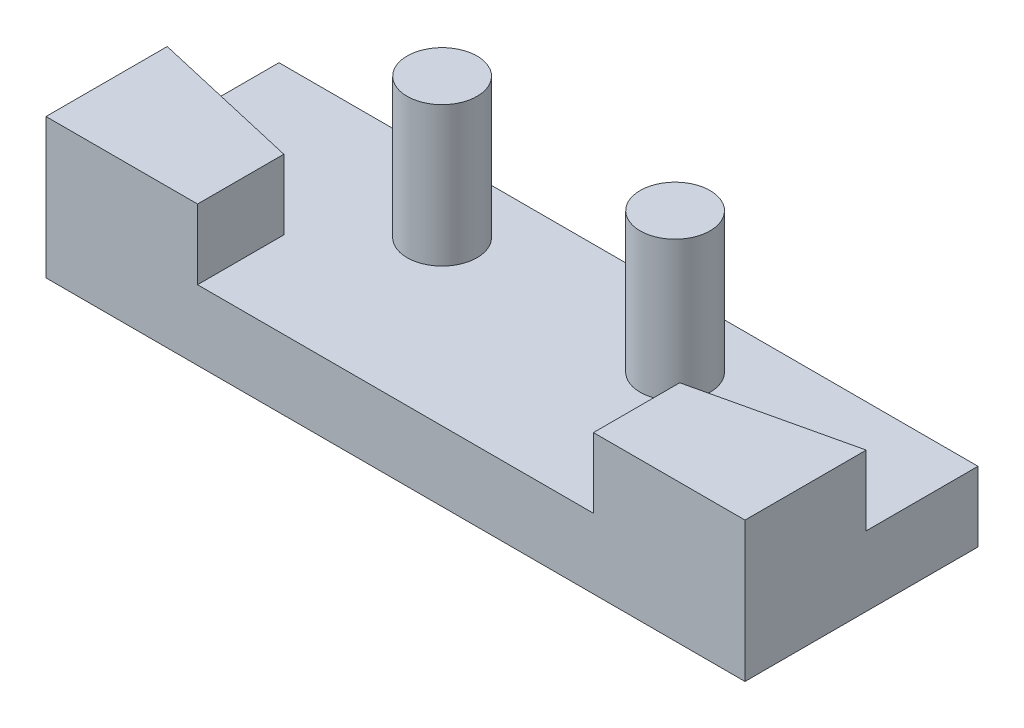
SolidWorks part; units mm, degrees
ref_plane "Front Plane" through (0, 0, 0) normal (0, 0, 1) x (1, 0, 0)
ref_plane "Top Plane" through (0, 0, 0) normal (0, 1, 0) x (1, 0, 0)
ref_plane "Right Plane" through (0, 0, 0) normal (1, 0, 0) x (0, 0, -1)
sketch "Sketch2" plane through (0, 0, 0) normal (0, 1, 0) x (1, 0, 0)
  line L1 (0, 0) -> (30, 0)
  line L2 (0, 0) -> (0, -10)
  line L3 (0, -10) -> (30, -10)
  line L4 (30, 0) -> (30, -10)
  dimension "D1" = 30
  dimension "D2" = 10
extrude "Boss-Extrude2" add sketch "Sketch2" along normal blind 6
sketch "Sketch4" plane through (0, 6, 0) normal (0, 1, 0) x (1, 0, 0)
  line L0 (30, 0) -> (0, 0) construction
  line L1 (0, 0) -> (0, -10) construction
  line L2 (10, -3) -> (4.3125, -1.6869) construction
  line L3 (10, -3) -> (9.1002, -6.8975) construction
  line L4 (9.1002, -6.8975) -> (0, -4.7965) construction
  line L5 (0, -4.7965) -> (6.5043, -6.2982)
  line L6 (6.5043, -6.2982) -> (6.5043, -10)
  line L7 (0, -10) -> (30, -10) construction
  line L8 (6.5043, -10) -> (23.4957, -10)
  line L9 (0, -4.7965) -> (0, 0)
  line L10 (0, 0) -> (30, 0)
  line L11 (15, 0) -> (15, -10) construction
  line L12 (30, -4.7965) -> (30, 0)
  line L13 (23.4957, -6.2982) -> (23.4957, -10)
  line L14 (30, -4.7965) -> (23.4957, -6.2982)
  circle A0 centre (10, -3) radius 1.5
  circle A1 centre (20, -3) radius 1.5
  dimension "D1" = 3
  dimension "D3" = 3
  dimension "D2" = 3
  dimension "D4" = 10
  dimension "D5" = 10
  dimension "D6" = 3
  dimension "D7" = 13
  dimension "D8" = 4
  dimension "D9" = 90
extrude "Cut-Extrude1" cut sketch "Sketch4" against normal blind 3 contours L5 L6 L8 L13 L14 L12 L10 L9
extrude "Boss-Extrude4" add sketch "Sketch4<4>" along normal blind 3 separate body contours A0 | A1 region at (10, 6, 3) region at (20, 6, 3)
sketch "Sketch4<4>" plane through (0, 6, 0) normal (0, 1, 0) x (1, 0, 0) same geometry as "Sketch4"
extrude "Boss-Extrude5" add sketch "Sketch4<5>" against normal blind 3 contours A0 | A1
sketch "Sketch4<5>" plane through (0, 6, 0) normal (0, 1, 0) x (1, 0, 0) same geometry as "Sketch4"
